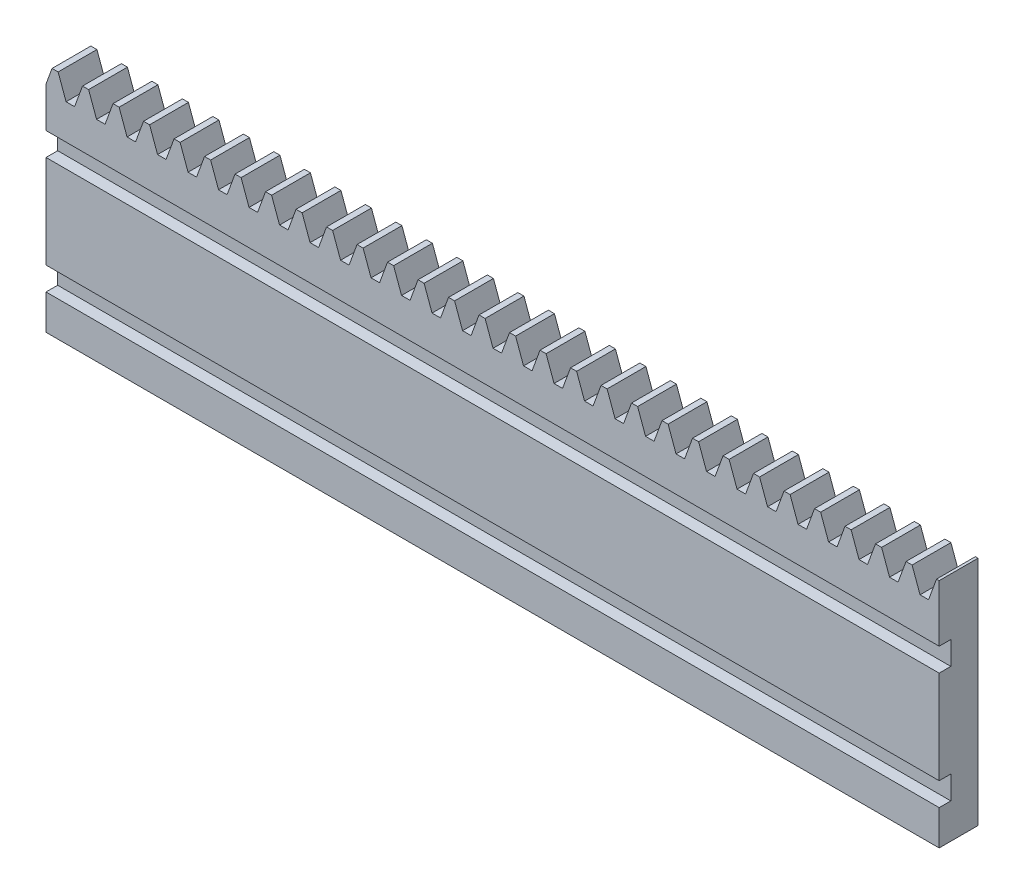
SolidWorks part; units mm, degrees
extrude "Blank" add sketch "BlankSke" against normal blind 5
sketch "BlankSke" plane through (0, 0, 0) normal (0, 0, 1) x (1, 0, 0)
  line L1 (0, 0) -> (320, 0)
  line L2 (0, 0) -> (0, 41.25)
  line L3 (0, 41.25) -> (320, 41.25)
  line L4 (320, 0) -> (320, 41.25)
  dimension "Length" = 320
ref_plane "Plane1" through (0, 0, 0) normal (0, 0, 1) x (1, 0, 0)
ref_plane "Plane2" through (0, 0, 0) normal (0, 1, 0) x (1, 0, 0)
ref_plane "Plane3" through (0, 0, 0) normal (1, 0, 0) x (0, 0, -1)
sketch "HoldingSke" plane through (0, 0, 0) normal (0, 1, 0) x (1, 0, 0)
  line L0 (0, 0) -> (0.1113, 0.7922)
  line L1 (-15, 0) -> (100, 0) construction
  line L2 (0, 0) -> (-2.1039, 2.3779)
  line L3 (0, 0) -> (-11.863, 4.5341)
  line L4 (0, 0) -> (1.0525, 8.5716)
  line L5 (0, 0) -> (-23.7986, -8.8762)
  line L6 (0, 0) -> (-10.5278, -7.1032)
  line L9 (-71.009, 38.7566) -> (229.6927, 148.2031)
  line L10 (-76.2, 3.6279) -> (-36.2, 3.6279)
  line L11 (0, 0) -> (-5, 0)
  line L12 (-76.2, 101.6) -> (-76.155, 101.6)
  line L13 (24.9733, 27.94) -> (52.9518, 28.4284)
  line L14 (24.9733, 27.94) -> (24.9743, 27.94)
  line L15 (24.9733, 27.94) -> (100.4006, 29.5858)
  circle A0 centre (0, 0) radius 19.05
  circle A1 centre (0, 0) radius 20
  circle A2 centre (0, 0) radius 12.7
  dimension "Num_teeth" = 83
  dimension "Width" = 5
  dimension "Length" = 320
  dimension "Pitch_height" = 40
sketch "TooCutSkeIll" plane through (0, 0, 0) normal (0, 0, 1) x (1, 0, 0)
  line L0 (-1.5597, 41.2171) -> (-0.6231, 38.6438)
  line L1 (-0.3285, 38.4375) -> (0.3285, 38.4375)
  line L2 (0.6231, 38.6438) -> (1.5597, 41.2171)
  line L3 (320, 41.25) -> (0, 41.25) construction
  line L4 (0, 0) -> (0, 64.897) construction
  line L5 (-13.208, 40) -> (12.954, 40) construction
  line L6 (0, 0) -> (320, 0) construction
  line L7 (1.1167, 40) -> (1.1167, 48.7463) construction
  line L8 (-1.1167, 40) -> (-1.1167, 48.7463) construction
  line L9 (1.6067, 41.25) -> (1.6067, 41.2754)
  line L10 (-1.6067, 41.25) -> (-1.6067, 41.2754)
  line L11 (-1.6067, 41.2754) -> (1.6067, 41.2754)
  arc A0 (0.3285, 38.4375) -> (0.6231, 38.6438) centre (0.3285, 38.751) ccw
  arc A1 (-0.6231, 38.6438) -> (-0.3285, 38.4375) centre (-0.3285, 38.751) ccw
  arc A2 (1.6067, 41.25) -> (1.5597, 41.2171) centre (1.6067, 41.2) ccw
  arc A3 (-1.5597, 41.2171) -> (-1.6067, 41.25) centre (-1.6067, 41.2) ccw
  dimension "Addendum_plus" = 1.2754
  dimension "Pitch_height" = 40
  dimension "Pressure_angle" = 20
  dimension "Gap_width" = 2.2335
  dimension "Dedendum" = 1.5625
extrude "ToothCutIll" [suppressed] cut sketch "TooCutSkeIll" against normal through all
sketch "TooCutSkeSim" plane through (0, 0, 0) normal (0, 0, 1) x (1, 0, 0)
  line L0 (0.548, 38.4375) -> (-0.548, 38.4375)
  line L1 (1.581, 41.2754) -> (0.548, 38.4375)
  line L2 (0, 17.4625) -> (0, 53.467) construction
  line L3 (1.581, 41.2754) -> (-1.581, 41.2754)
  line L6 (-1.581, 41.2754) -> (-0.548, 38.4375)
  line L9 (-1.1167, 40) -> (1.1167, 40) construction
  line L10 (0, 0) -> (320, 0) construction
  line L11 (1.1167, 40) -> (1.1167, 53.467) construction
  line L12 (-1.1167, 40) -> (-1.1167, 53.467) construction
  dimension "Addendum_plus" = 1.2754
  dimension "Pitch_height" = 40
  dimension "Pressure_angle" = 20
  dimension "Gap_width" = 2.2335
  dimension "Dedendum" = 1.5625
extrude "ToothCutSim" cut sketch "TooCutSkeSim" against normal through all
pattern_linear "TeethCuts" count 83 spacing 3.927 along (1, 0, 0) of "ToothCutIll", "ToothCutSim"
sketch "Schizzo4" plane through (320, 0, 0) normal (1, 0, 0) x (0, 0, -1)
  line L0 (5, 0) -> (5, 41.25) construction
  line L1 (0, 0) -> (5, 0)
  line L2 (0, 0) -> (0, 11.438)
  line L3 (0, 11.438) -> (5, 11.438)
  line L4 (5, 0) -> (5, 11.438)
  line L6 (5, 41.25) -> (0, 41.25) construction
  point P9 (2.5, 11.438)
  dimension "D1" = 29.812
extrude "Taglio-Estrusione1" cut sketch "Schizzo4" against normal blind 359
sketch "Schizzo5" plane through (320, 0, 0) normal (1, 0, 0) x (0, 0, -1)
  line L0 (0, 11.438) -> (0, 41.25) construction
  line L1 (0, 33.937) -> (1.5, 33.937)
  line L2 (0, 33.937) -> (0, 30.937)
  line L3 (0, 30.937) -> (1.5, 30.937)
  line L4 (1.5, 33.937) -> (1.5, 30.937)
  line L5 (5, 41.25) -> (0, 41.25) construction
  line L6 (0, 18.938) -> (1.5, 18.938)
  line L7 (0, 18.938) -> (0, 15.938)
  line L8 (0, 15.938) -> (1.5, 15.938)
  line L9 (1.5, 18.938) -> (1.5, 15.938)
  line L10 (5, 11.438) -> (0, 11.438) construction
  point P10 (0, 38.437)
  dimension "D1" = 2.813
  dimension "D2" = 4.5
  dimension "D3" = 4.5
  dimension "D4" = 1.5
  dimension "D5" = 1.5
  dimension "D6" = 3
  dimension "D7" = 3
extrude "Taglio-Estrusione2" cut sketch "Schizzo5" against normal through all
sketch "Schizzo6" plane through (0, 0, -5) normal (0, 0, -1) x (-1, 0, 0)
  line L0 (-320, 11.438) -> (-205, 11.438)
  line L1 (-320, 11.438) -> (-320, 41.25)
  line L2 (-205, 11.438) -> (-205, 41.25)
  line L3 (-320, 41.25) -> (-205, 41.25)
  line L4 (0, 11.438) -> (-320, 11.438) construction
  line L5 (-269.3907, 41.25) -> (-268.6071, 41.25) construction
  point P7 (-268.9989, 41.25)
  dimension "D1" = 115
extrude "Taglio-Estrusione3" cut sketch "Schizzo6" against normal blind 10 and the other way blind 10 flip side to cut
equation "' \"Module@HoldingSke\" = 6.35"
equation "' \"Num_teeth@HoldingSke\" = 12"
equation "' \"Ap@HoldingSke\" =  20"
equation "' \"Ap@HoldingSke\" = 20"
equation "' \"Width@HoldingSke\" = 0.25 * 25.4"
equation "' \"Show_teeth@HoldingSke\" = 500"
equation "' \"Backlash@HoldingSke\" = 0.009 * 25.4"
equation "' \"Addendum_fac@HoldingSke\" = 1.0"
equation "' \"Dedendum_fac@HoldingSke\" = 1.25"
equation "' \"Dedendum_add@HoldingSke\" = 0.00005 * 25.4"
equation "' \"Clearance_fac@HoldingSke\" = 0.25"
equation "' \"Pitch_height@HoldingSke\" = 1 * 25.4"
equation "' \"Length@HoldingSke\" = 4.71 * 25.4"
equation "\"Pitch@HoldingSke\" = 1 / \"Module@HoldingSke\""
equation "\"MPH@HoldingSke\" = \"Dedendum_fac@HoldingSke\" / \"Pitch@HoldingSke\" + 2 * \"Dedendum_add@HoldingSke\" + 0.002 * 25.4"
equation "\"MPH@HoldingSke\" = ((sgn( \"MPH@HoldingSke\" - \"Pitch_height@HoldingSke\")+1)*( \"MPH@HoldingSke\" - \"Pitch_height@HoldingSke\"))/2 + \"Pitch_height@HoldingSke\""
equation "\"Blank_height@BlankSke\" = \"Pitch_height@HoldingSke\" + \"Addendum_fac@HoldingSke\"  / \"Pitch@HoldingSke\" "
equation "\"Length@BlankSke\" =  \"Length@HoldingSke\""
equation "\"Face_width@Blank\" = \"Width@HoldingSke\""
equation "\"Pressure_angle@TooCutSkeIll\" = \"Ap@HoldingSke\""
equation "\"Addendum_plus@TooCutSkeIll\" =  \"Addendum_fac@HoldingSke\"  / \"Pitch@HoldingSke\" + 0.001 *25.4"
equation "\"Dedendum@TooCutSkeIll\" = \"Dedendum_fac@HoldingSke\"  / \"Pitch@HoldingSke\""
equation "\"Pitch_height@TooCutSkeIll\" =  \"MPH@HoldingSke\""
equation "\"Gap_width@TooCutSkeIll\" = 3.14159265 / 2 / \"Pitch@HoldingSke\" + 6 * \"Backlash@HoldingSke\""
equation "\"Pressure_angle@TooCutSkeSim\" = \"Ap@HoldingSke\""
equation "\"Addendum_plus@TooCutSkeSim\" =  \"Addendum_fac@HoldingSke\"  / \"Pitch@HoldingSke\" + 0.001 * 25.4"
equation "\"Dedendum@TooCutSkeSim\" = \"Dedendum_fac@HoldingSke\"  / \"Pitch@HoldingSke\""
equation "\"Pitch_height@TooCutSkeSim\" =  \"MPH@HoldingSke\""
equation "\"Gap_width@TooCutSkeSim\" = 3.14159265 / 2 / \"Pitch@HoldingSke\" + 6 * \"Backlash@HoldingSke\""
equation "\"Root_fillet@TooCutSkeIll\" = \"Clearance_fac@HoldingSke\" / \"Pitch@HoldingSke\" + \"Dedendum_add@HoldingSke\""
equation "\"Break_rad@TooCutSkeIll\" = 0.02 / \"Pitch@HoldingSke\" * 2"
equation "\"Linear_pitch@TeethCuts\" = 3.14159265 / \"Pitch@HoldingSke\""
equation "\"Num_teeth@HoldingSke\" = int( ( \"Length@HoldingSke\" + 0 ) / (3.14159265 / \"Pitch@HoldingSke\")) + 0.9999  + 1"
equation " \"Num_teeth@TeethCuts\" = int( \"Show_teeth@HoldingSke\" ) + 1"
equation " \"Num_teeth@TeethCuts\" = ((sgn( \"Num_teeth@TeethCuts\" - \"Num_teeth@HoldingSke\" )-1)*( \"Num_teeth@TeethCuts\" - \"Num_teeth@HoldingSke\" ))/-2+ \"Num_teeth@HoldingSke\""
equation " \"Num_teeth@TeethCuts\" = ((sgn( \"Num_teeth@TeethCuts\" - 2.0)+1)*( \"Num_teeth@TeethCuts\" - 2.0))/2 +2.0"
